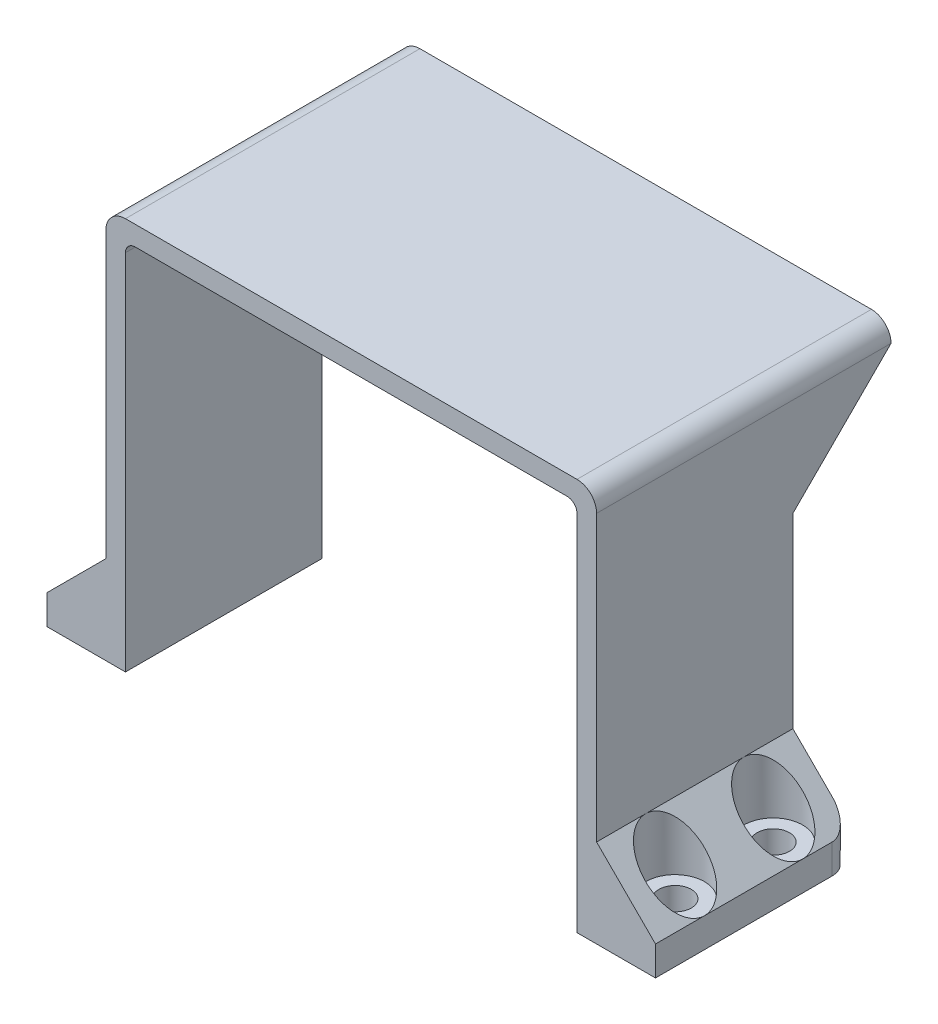
SolidWorks part; units mm, degrees
ref_plane "前视基准面" through (0, 0, 0) normal (0, 0, 1) x (1, 0, 0)
ref_plane "上视基准面" through (0, 0, 0) normal (0, 1, 0) x (1, 0, 0)
ref_plane "右视基准面" through (0, 0, 0) normal (1, 0, 0) x (0, 0, -1)
sketch "草图1" plane through (0, 0, 0) normal (0, 1, 0) x (1, 0, 0)
  line L1 (-25, -10) -> (25, -10)
  line L2 (-25, -10) -> (-25, 10)
  line L3 (-25, 10) -> (25, 10)
  line L4 (25, -10) -> (25, 10)
  line L5 (-25, -10) -> (25, 10) construction
  line L6 (-25, 10) -> (25, -10) construction
  point P0 (0, 0)
  dimension "D1" = 20
  dimension "D2" = 50
extrude "凸台-拉伸1" add sketch "草图1" along normal blind 40
sketch "草图2" plane through (0, 0, 0) normal (0, 1, 0) x (1, 0, 0)
  line L0 (-27, 0) -> (27, 0) construction
  line L2 (-23, 10) -> (-31, 10)
  line L3 (-23, 10) -> (-23, -10)
  line L4 (-23, -10) -> (-31, -10)
  line L5 (-31, 10) -> (-31, -10)
  line L6 (-23, 10) -> (-31, -10) construction
  line L7 (-23, -10) -> (-31, 10) construction
  point P4 (0, 0)
  dimension "D1" = 54
  dimension "D2" = 8
  dimension "D3" = 20
extrude "凸台-拉伸2" add sketch "草图2" along normal blind 3
sketch "草图3" plane through (0, 3, 0) normal (0, 1, 0) x (1, 0, 0)
  line L0 (-31, 0) -> (-28, 0) construction
  line L1 (-28, 5) -> (-28, -5) construction
  line L2 (-31, 10) -> (-31, -10) construction
  circle A0 centre (-28, 5) radius 1.65
  circle A1 centre (-28, -5) radius 1.65
  point P7 (-28, 0)
  dimension "D2" = 3.3
  dimension "D1" = 10
  dimension "D3" = 3
extrude "切除-拉伸1" cut sketch "草图3" against normal up to next
mirror "镜向2" about plane through (0, 0, 0) normal (1, 0, 0) of "切除-拉伸1", "凸台-拉伸2"
chamfer "倒角1" distance 6 angle 45 2 edges at (-25, 3, 0) (25, 3, 0)
sketch "草图5" plane through (0, 40, 0) normal (0, 1, 0) x (1, 0, 0)
  circle A0 centre (-28, 5) radius 3
  circle A1 centre (-28, -5) radius 3
  dimension "D1" = 6
extrude "切除-拉伸3" cut sketch "草图5" against normal offset from surface (37 mm away) 3 up to face at (28, 0, -6.65)
mirror "镜向3" about plane through (0, 0, 0) normal (1, 0, 0) of "切除-拉伸3"
sketch "草图4" plane through (0, 0, 10) normal (0, 0, 1) x (1, 0, 0)
  line L0 (0, 0) -> (0, 19) construction
  line L1 (-25, 40) -> (25, 40) construction
  line L2 (-23, 0) -> (23, 0)
  line L3 (-23, 0) -> (-23, 38)
  line L4 (-23, 38) -> (23, 38)
  line L5 (23, 0) -> (23, 38)
  line L6 (-23, 0) -> (23, 38) construction
  line L7 (-23, 38) -> (23, 0) construction
  line L8 (-25, 40) -> (-25, 9) construction
  line L9 (-31, 0) -> (31, 0) construction
  point P11 (23, 0)
  dimension "D1" = 2
  dimension "D2" = 2
extrude "切除-拉伸2" cut sketch "草图4" against normal up to next
sketch "草图6" plane through (0, 0, -10) normal (0, 0, 1) x (1, 0, 0)
  line L0 (25, 40) -> (25, 9) construction
  line L1 (-25, 40) -> (25, 40)
  line L2 (-25, 40) -> (-25, 38)
  line L3 (-25, 38) -> (25, 38)
  line L4 (25, 40) -> (25, 38)
  line L5 (23, 38) -> (-23, 38) construction
  point P5 (25, 34.5889)
extrude "凸台-拉伸3" add sketch "草图6" against normal blind 10
chamfer "倒角2" distance 10 angle 45 1 edges at (24, 38, -10)
fillet "圆角1" radius 1 2 edges at (-23, 38, -5) (23, 38, -5)
fillet "圆角2" radius 2 2 edges at (-25, 40, -5) (25, 40, -5)
fillet "圆角3" radius 2 2 edges at (-31, 1.5, -10) (31, 1.5, -10)
